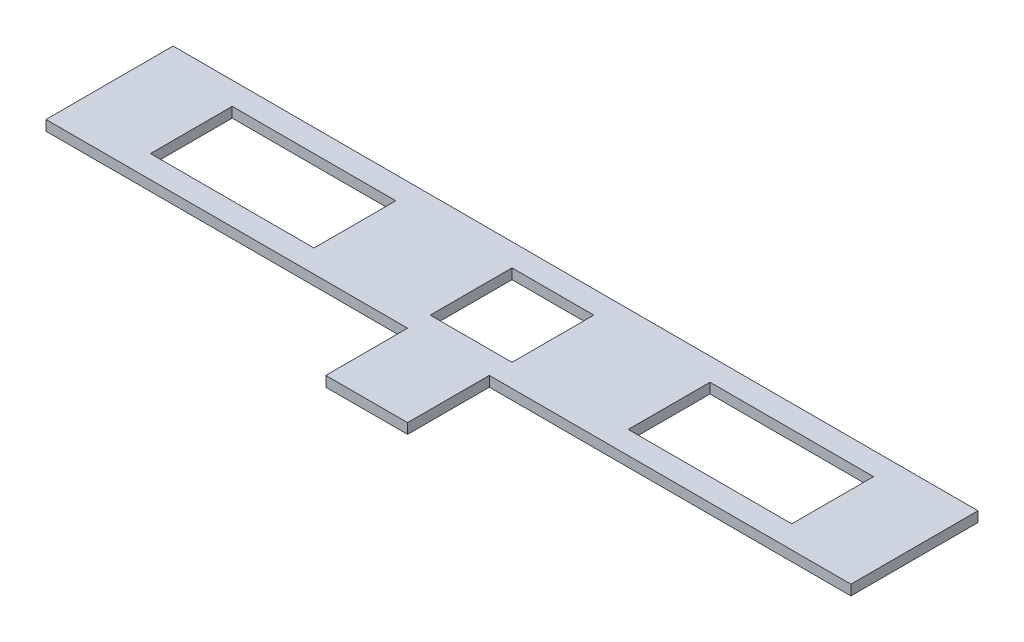
SolidWorks part; units mm, degrees
ref_plane "Front Plane" through (0, 0, 0) normal (0, 0, 1) x (1, 0, 0)
ref_plane "Top Plane" through (0, 0, 0) normal (0, 1, 0) x (1, 0, 0)
ref_plane "Right Plane" through (0, 0, 0) normal (1, 0, 0) x (0, 0, -1)
sketch "Sketch1" plane through (0, 0, 0) normal (0, 1, 0) x (1, 0, 0)
  line L0 (0, 78.962) -> (1000.0005, 78.962) construction
  line L2 (0, 0) -> (0, 157.9241)
  line L3 (0, 157.9241) -> (1000.0005, 157.9241)
  line L4 (1000.0005, 0) -> (1000.0005, 157.9241)
  line L9 (101.6, 28.162) -> (304.8, 28.162)
  line L10 (101.6, 28.162) -> (101.6, 129.762)
  line L12 (304.8, 28.162) -> (304.8, 129.762)
  line L17 (0, -31.5189) -> (406.4, -31.5189) construction
  line L18 (0, -31.5189) -> (0, -107.7189) construction
  line L19 (0, -107.7189) -> (406.4, -107.7189) construction
  line L20 (406.4, -31.5189) -> (406.4, -107.7189) construction
  line L21 (593.6005, -31.5189) -> (1000.0005, -31.5189) construction
  line L22 (593.6005, -31.5189) -> (593.6005, -107.7189) construction
  line L23 (593.6005, -107.7189) -> (1000.0005, -107.7189) construction
  line L24 (1000.0005, -31.5189) -> (1000.0005, -107.7189) construction
  line L25 (203.2, -31.5189) -> (203.2, -107.7189) construction
  line L26 (796.8005, -107.7189) -> (796.8005, -31.5189) construction
  line L27 (203.2, -31.5189) -> (203.2, 157.9241) construction
  line L28 (796.8005, -31.5189) -> (796.8005, 157.9241) construction
  line L29 (500.0003, -101.6) -> (500.0003, 157.9241) construction
  line L30 (0, 0) -> (449.2003, 0)
  line L32 (449.2003, -101.6) -> (449.2003, 0)
  line L33 (550.8003, -101.6) -> (550.8003, 0)
  line L35 (101.6, 129.762) -> (304.8, 129.762)
  line L36 (449.2003, 129.762) -> (550.8003, 129.762)
  line L37 (449.2003, 129.762) -> (449.2003, 28.162)
  line L38 (449.2003, 28.162) -> (550.8003, 28.162)
  line L39 (550.8003, 129.762) -> (550.8003, 28.162)
  line L40 (449.2003, 129.762) -> (550.8003, 28.162) construction
  line L41 (449.2003, 28.162) -> (550.8003, 129.762) construction
  line L42 (695.2005, 28.162) -> (695.2005, 129.762)
  line L43 (898.4005, 28.162) -> (695.2005, 28.162)
  line L44 (898.4005, 28.162) -> (898.4005, 129.762)
  line L45 (898.4005, 129.762) -> (695.2005, 129.762)
  line L46 (550.8003, 0) -> (1000.0005, 0)
  line L47 (550.8003, -101.6) -> (449.2003, -101.6)
  point P36 (500.0003, 78.962)
  point P41 (101.6, 78.962)
  dimension "D1" = 406.4
  dimension "D2" = 76.2
  dimension "D3" = 1000.0005
  dimension "D4" = 101.6
  dimension "D5" = 101.6
  dimension "D6" = 203.2
extrude "Boss-Extrude1" add sketch "Sketch1" along normal blind 12.7
